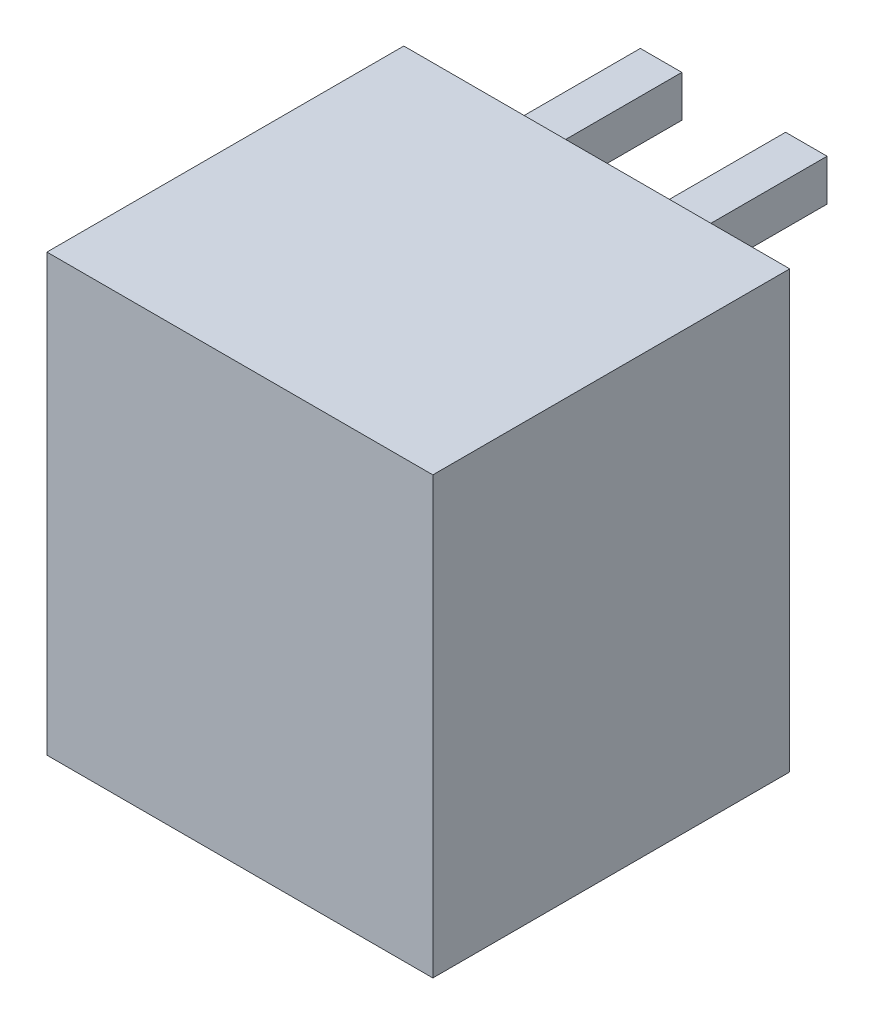
SolidWorks part; units mm, degrees
ref_plane "Спереди" through (0, 0, 0) normal (0, 0, 1) x (1, 0, 0)
ref_plane "Сверху" through (0, 0, 0) normal (0, 1, 0) x (1, 0, 0)
ref_plane "Справа" through (0, 0, 0) normal (1, 0, 0) x (0, 0, -1)
sketch "Эскиз1" plane through (0, 0, 0) normal (0, 0, 1) x (1, 0, 0)
  line L1 (-4.65, 0) -> (4.65, 0)
  line L2 (-4.65, 0) -> (-4.65, 10.5)
  line L3 (-4.65, 10.5) -> (4.65, 10.5)
  line L4 (4.65, 0) -> (4.65, 10.5)
  point P0 (0, 0)
  point P6 (0, 0)
  dimension "D1" = 9.3
  dimension "D2" = 10.5
extrude "Бобышка-Вытянуть1" add sketch "Эскиз1" along normal blind 8.6
sketch "Эскиз2" plane through (0, 0, 0) normal (0, -1, 0) x (1, 0, 0)
  line L0 (-3.65, 6.6) -> (3.65, 6.6)
  line L1 (3.65, 6.6) -> (3.65, 0.2)
  line L2 (3.65, 0.2) -> (1.45, 0.2)
  line L3 (1.45, 0.2) -> (1.45, 1.8)
  line L4 (1.45, 1.8) -> (0.15, 1.8)
  line L5 (0.15, 1.8) -> (0.15, 0.2)
  line L6 (0.15, 0.2) -> (-2.05, 0.2)
  line L7 (-3.65, 6.6) -> (-3.65, 1.8)
  line L8 (-3.65, 1.8) -> (-2.05, 1.8)
  line L9 (-2.05, 1.8) -> (-2.05, 0.2)
  line L10 (4.65, 8.6) -> (4.65, 0) construction
  line L11 (-4.65, 8.6) -> (-4.65, 0) construction
  line L12 (-4.65, 8.6) -> (4.65, 8.6) construction
  dimension "D1" = 4.8
  dimension "D2" = 6.4
  dimension "D3" = 2.2
  dimension "D4" = 2.2
  dimension "D5" = 3.2
  dimension "D6" = 4.8
  dimension "D7" = 1
  dimension "D8" = 2
extrude "Вырез-Вытянуть1" cut sketch "Эскиз2" against normal blind 7
sketch "Эскиз3" plane through (0, 0, 0) normal (0, 0, -1) x (-1, 0, 0)
  line L0 (4.65, 0) -> (-4.65, 0) construction
  line L1 (2.25, 10) -> (1.25, 10)
  line L2 (2.25, 10) -> (2.25, 9)
  line L3 (2.25, 9) -> (1.25, 9)
  line L4 (1.25, 10) -> (1.25, 9)
  line L5 (2.25, 10) -> (1.25, 9) construction
  line L6 (2.25, 9) -> (1.25, 10) construction
  line L7 (4.65, 10.5) -> (4.65, 0) construction
  point P0 (1.75, 9.5)
  dimension "D1" = 1
  dimension "D2" = 9.5
  dimension "D3" = 2.9
extrude "Бобышка-Вытянуть2" add sketch "Эскиз3" along normal blind 3.6 and the other way blind 5
chamfer "Фаска1" distance 0.3 distance2 0.3 4 edges at (-1.25, 9.5, -3.6) (-1.75, 9, -3.6) (-2.25, 9.5, -3.6) (-1.75, 10, -3.6)
sketch "Эскиз4" plane through (0, 7, 0) normal (0, -1, 0) x (1, 0, 0)
  line L0 (-2.25, 0) -> (-2.25, -3.3) construction
  line L1 (-2.25, 3.85) -> (-1.25, 3.85)
  line L2 (-2.25, 3.85) -> (-2.25, 4.85)
  line L3 (-2.25, 4.85) -> (-1.25, 4.85)
  line L4 (-1.25, 3.85) -> (-1.25, 4.85)
  line L5 (-1.25, 0) -> (-1.25, -3.3) construction
  line L7 (-4.65, 0) -> (4.65, 0) construction
  dimension "D1" = 3.85
extrude "Бобышка-Вытянуть3" add sketch "Эскиз4" along normal blind 5
pattern_linear "Линейный массив1" count 2 spacing 3.5 along (1, 0, 0) of "Бобышка-Вытянуть2", "Фаска1", "Бобышка-Вытянуть3"
equation "\"N\"= 2"
equation "\"D1@Эскиз1\"= ( \"N\" - 1 ) * 3.5 + 5.8"
equation "\"D1@Линейный массив1\"=\"N\""
